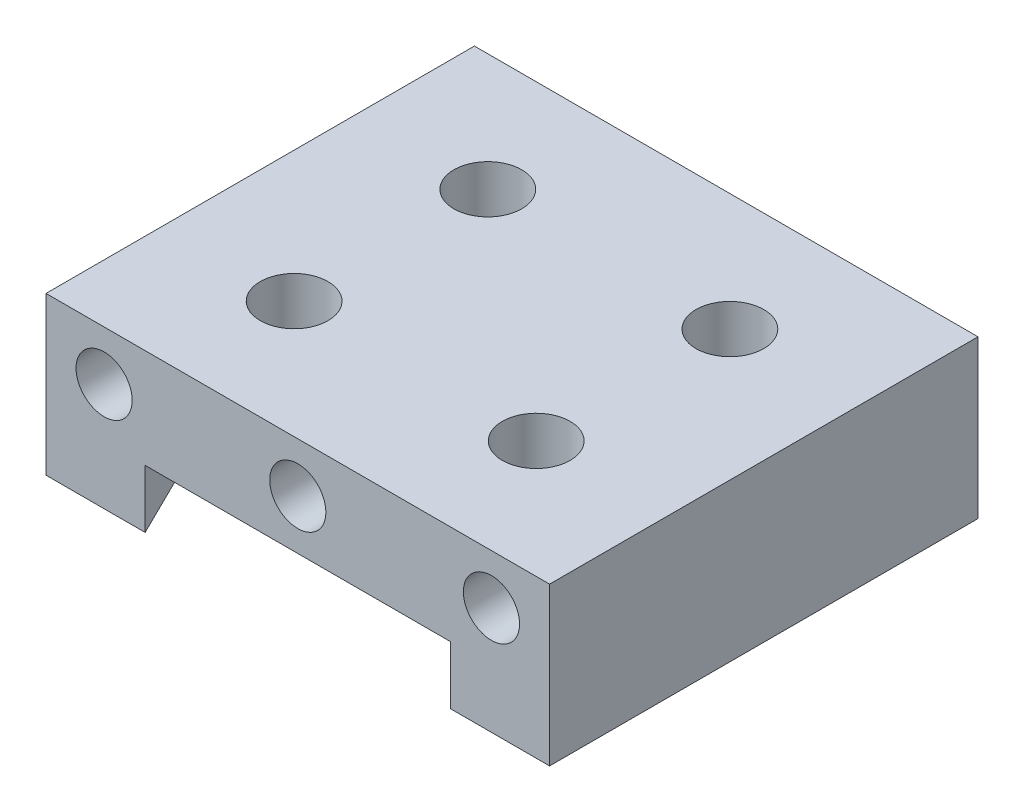
SolidWorks part; units mm, degrees
ref_plane "Front Plane" through (0, 0, 0) normal (0, 0, 1) x (1, 0, 0)
ref_plane "Top Plane" through (0, 0, 0) normal (0, 1, 0) x (1, 0, 0)
ref_plane "Right Plane" through (0, 0, 0) normal (1, 0, 0) x (0, 0, -1)
sketch "Sketch1" plane through (0, 0, 0) normal (0, 1, 0) x (1, 0, 0)
  line L5 (0, 0) -> (16.0528, 0) construction
  line L6 (0, 0) -> (0, -25.9338) construction
  line L7 (-6.25, 5) -> (-6.25, -5) construction
  line L8 (-6.25, 0) -> (0, 0) construction
  line L10 (-13, 11.06) -> (13, 11.06)
  line L11 (-13, 11.06) -> (-13, -11.06)
  line L12 (-13, -11.06) -> (13, -11.06)
  line L13 (13, 11.06) -> (13, -11.06)
  line L14 (-13, 11.06) -> (13, -11.06) construction
  line L15 (-13, -11.06) -> (13, 11.06) construction
  circle A7 centre (-6.25, 5) radius 1.75
  circle A8 centre (-6.25, -5) radius 1.75
  circle A9 centre (6.25, -5) radius 1.75
  circle A10 centre (6.25, 5) radius 1.75
  point P1 (0, 0)
  dimension "D3" = 3.5
  dimension "D4" = 12.5
  dimension "D5" = 10
  dimension "D7" = 26
  dimension "D8" = 6.06
extrude "Boss-Extrude1" add sketch "Sketch1" along normal blind 5.13 contours L13 L10 L11 L12 A9 A8 A7 A10 region at (0, 0, 0)
sketch "Sketch2" plane through (0, 0, 11.06) normal (0, 0, 1) x (1, 0, 0)
  line L0 (-13, 2.565) -> (13, 2.565) construction
  line L1 (-13, 5.13) -> (-13, 0) construction
  line L2 (13, 5.13) -> (13, 0) construction
  line L3 (0, 0) -> (0, 5.13) construction
  line L4 (-13, 5.13) -> (13, 5.13) construction
  circle A0 centre (0, 2.565) radius 1.45
  circle A1 centre (-10, 2.565) radius 1.45
  circle A2 centre (10, 2.565) radius 1.45
  dimension "D1" = 2.9
  dimension "D2" = 10
extrude "Cut-Extrude1" cut sketch "Sketch2" against normal up to next
sketch "Sketch3" plane through (0, 0, 0) normal (0, -1, 0) x (1, 0, 0)
  line L6 (-11.035, -11.06) -> (11.035, -11.06)
  line L7 (0, -11.06) -> (0, 2.57) construction
  line L8 (-13, -11.06) -> (13, -11.06) construction
  line L9 (-11.63, 2.57) -> (11.63, 2.57)
  line L10 (0, 2.57) -> (0, -11.06) construction
  line L11 (11.035, -11.06) -> (11.63, 2.57)
  line L12 (-11.035, -11.06) -> (-11.63, 2.57)
  line L13 (-10.92, 4.9) -> (10.92, 4.9)
  line L14 (0, 4.9) -> (0, -11.06) construction
  line L15 (-7.625, 11.58) -> (7.625, 11.58)
  line L16 (0, 11.58) -> (0, -11.06) construction
  line L17 (-7.625, 11.58) -> (-10.92, 4.9)
  line L18 (10.92, 4.9) -> (7.625, 11.58)
  line L19 (-7.8815, 11.06) -> (7.8815, 11.06)
  line L20 (-13, 11.06) -> (13, 11.06) construction
  line L22 (-13, 11.06) -> (13, 11.06)
  line L23 (-13, 11.06) -> (-13, -11.06)
  line L24 (-13, -11.06) -> (13, -11.06)
  line L25 (13, 11.06) -> (13, -11.06)
  spline S0 degree 2 poles (-11.63, 2.57) (-11.3495, 3.7585) (-10.92, 4.9) knots 0 0 0 1 1 1
  spline S1 degree 2 poles (11.63, 2.57) (11.3495, 3.7585) (10.92, 4.9) knots 0 0 0 1 1 1
  line M4 (13, -11.06) -> (13, 11.06)
  line M5 (13, 11.06) -> (-13, 11.06)
  line M6 (-13, 11.06) -> (-13, -11.06)
  line M7 (-13, -11.06) -> (13, -11.06)
  dimension "D8" = 22.07
  dimension "D9" = 23.26
  dimension "D11" = 13.63
  dimension "D12" = 21.84
  dimension "D14" = 2.33
  dimension "D15" = 15.25
  dimension "D17" = 6.68
extrude "Boss-Extrude2" add sketch "Sketch3" along normal blind 3 contours L12 S0 L17 M5 M6 M7 | S1 L11 L18 M7 M4 M5 region at (-11.6731, 0, 1.9638) region at (11.6731, 0, 1.9638)
